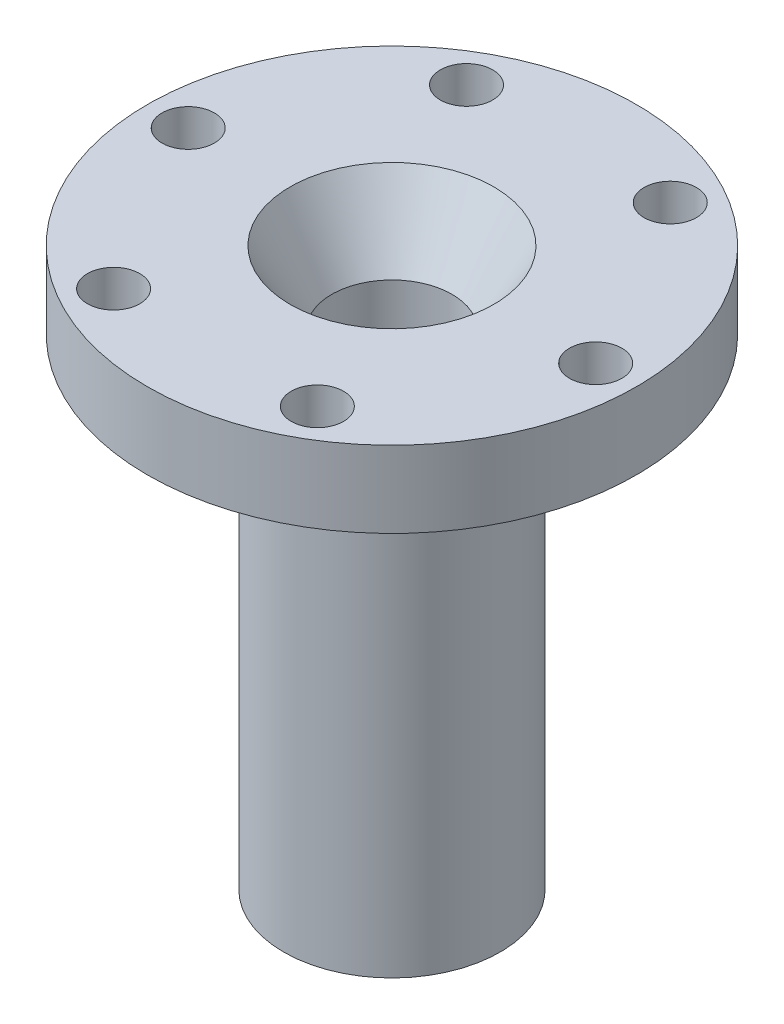
SolidWorks part; units mm, degrees
material "AISI Type 316L stainless steel"
ref_plane "Front Plane" through (0, 0, 0) normal (0, 0, 1) x (1, 0, 0)
ref_plane "Top Plane" through (0, 0, 0) normal (0, 1, 0) x (1, 0, 0)
ref_plane "Right Plane" through (0, 0, 0) normal (1, 0, 0) x (0, 0, -1)
sketch "Sketch1" plane through (0, 0, 0) normal (0, 0, 1) x (1, 0, 0)
  line L0 (0, 0) -> (0, -29.8554) construction
  line L1 (7.5, -69.525) -> (7.5, -9.0067)
  line L2 (7.5, -9.0067) -> (12.7, 0)
  line L3 (12.7, 0) -> (30.48, 0)
  line L4 (30.48, 0) -> (30.48, -9.525)
  line L5 (30.48, -9.525) -> (13.5, -9.525)
  line L6 (13.5, -9.525) -> (13.5, -69.525)
  line L7 (13.5, -69.525) -> (7.5, -69.525)
  dimension "D1" = 27
  dimension "D2" = 15
  dimension "D3" = 60
  dimension "D4" = 30
  dimension "D5" = 25.4
  dimension "D6" = 60.96
  dimension "D7" = 9.525
revolve "Revolve1" add sketch "Sketch1" angle 360 about L0
hole_wizard "1/4 Clearance Hole1" positions "Sketch3" profile "Sketch4" hole size "1/4" standard "ANSI Inch" end condition through all
sketch "Sketch3" plane through (0, 0, 0) normal (0, 1, 0) x (1, 0, 0)
  line L0 (25.4, 0) -> (0, 0) construction
  point P0 (25.4, 0)
  dimension "D1" = 25.4
sketch "Sketch4" plane through (25.4, 0, 0) normal (1, 0, 0) x (0, 0, 1)
  line L0 (0, 0) -> (0, 69.525)
  line L1 (0, 69.525) -> (3.2639, 69.525)
  line L2 (3.2639, 69.525) -> (3.2639, 0)
  line L5 (3.2639, 0) -> (0, 0)
  line L11 (0, -6.35) -> (0, 107.95) construction
  dimension "Thru Hole Dia." = 6.5278
  dimension "Thru Hole Depth" = 69.525
pattern_circular "CirPattern1" count 6 over 360 about axis through (0, 0, 0) along (0, 1, 0) of "1/4 Clearance Hole1" reverse direction yes
sketch "Sketch5" plane through (0, 0, 0) normal (0, 1, 0) x (1, 0, 0)
  circle A0 centre (0, 0) radius 25.4
  dimension "D1" = 50.8
chamfer "Chamfer1" distance 2.032 angle 22 1 edges at (0, -69.525, 7.5) first distance on face at (0, -69.525, 13.5)
fillet "Fillet1" radius 0.7937 1 edges at (0, -68.704, 7.5)
chamfer "Chamfer2" distance 3.175 angle 45 1 edges at (0, -9.525, 13.5)
